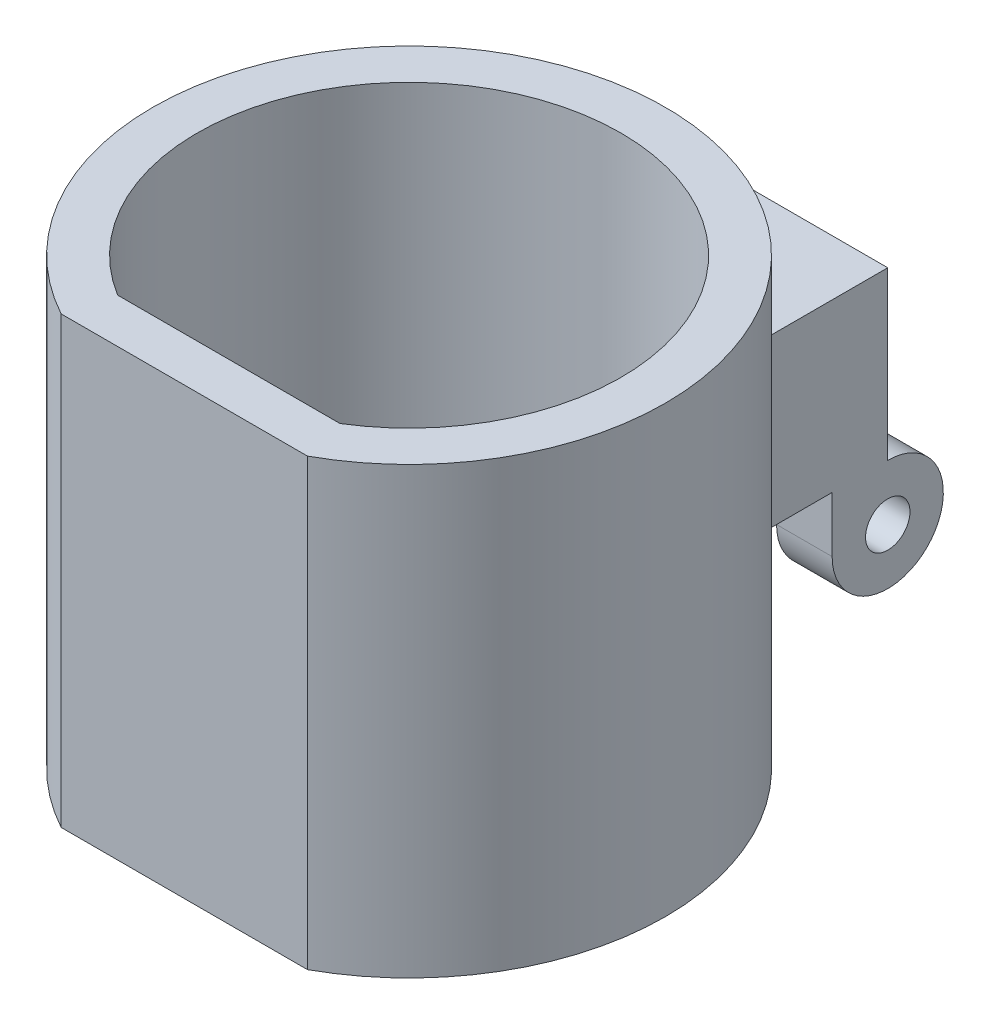
SolidWorks part; units mm, degrees
ref_plane "Front Plane" through (0, 0, 0) normal (0, 0, 1) x (1, 0, 0)
ref_plane "Top Plane" through (0, 0, 0) normal (0, 1, 0) x (1, 0, 0)
ref_plane "Right Plane" through (0, 0, 0) normal (1, 0, 0) x (0, 0, -1)
sketch "Sketch1" plane through (0, 0, 0) normal (0, 1, 0) x (1, 0, 0)
  line L0 (-10, -16.2143) -> (10, -16.2143)
  line L1 (-11.0764, -20.2143) -> (11.0764, -20.2143)
  arc A0 (10, -16.2143) -> (-10, -16.2143) centre (0, 0) ccw
  arc A1 (11.0764, -20.2143) -> (-11.0764, -20.2143) centre (0, 0) ccw
  dimension "D1" = 19.05
  dimension "D2" = 20
  dimension "D3" = 4
extrude "Boss-Extrude1" add sketch "Sketch1" along normal mid plane 40
ref_plane "Plane1" through (0, 0, -23.05) normal (0, 0, -1) x (-1, 0, 0)
sketch "Sketch2" plane through (0, 0, -23.05) normal (0, 0, -1) x (-1, 0, 0)
  line L1 (-10, -7.5) -> (10, -7.5)
  line L2 (-10, -7.5) -> (-10, 7.5)
  line L3 (-10, 7.5) -> (10, 7.5)
  line L4 (10, -7.5) -> (10, 7.5)
  line L5 (-10, -7.5) -> (10, 7.5) construction
  line L6 (-10, 7.5) -> (10, -7.5) construction
  point P0 (0, 0)
  dimension "D1" = 20
  dimension "D2" = 15
extrude "Boss-Extrude2" add sketch "Sketch2" against normal up to surface and the other way blind 10 up to face at (0, 0, -1.4179)
sketch "Sketch3" plane through (10, 0, 0) normal (1, 0, 0) x (0, 0, -1)
  line L1 (28.05, -12.5) -> (28.05, -7.5)
  line L2 (33.05, -7.5) -> (20.7678, -7.5) construction
  line L3 (28.05, -7.5) -> (33.05, -7.5)
  circle A0 centre (33.05, -12.5) radius 2
  arc A1 (28.05, -12.5) -> (33.05, -7.5) centre (33.05, -12.5) ccw
  circle A2 centre (33.05, -12.5) radius 5 construction
  arc A3 (28.05, -12.5) -> (33.05, -7.5) centre (33.05, -12.5) cw construction
  dimension "D1" = 4
  dimension "D2" = 3
extrude "Boss-Extrude3" add sketch "Sketch3" against normal blind 5
mirror "Mirror1" about plane through (0, 0, 0) normal (1, 0, 0) of "Boss-Extrude3"
